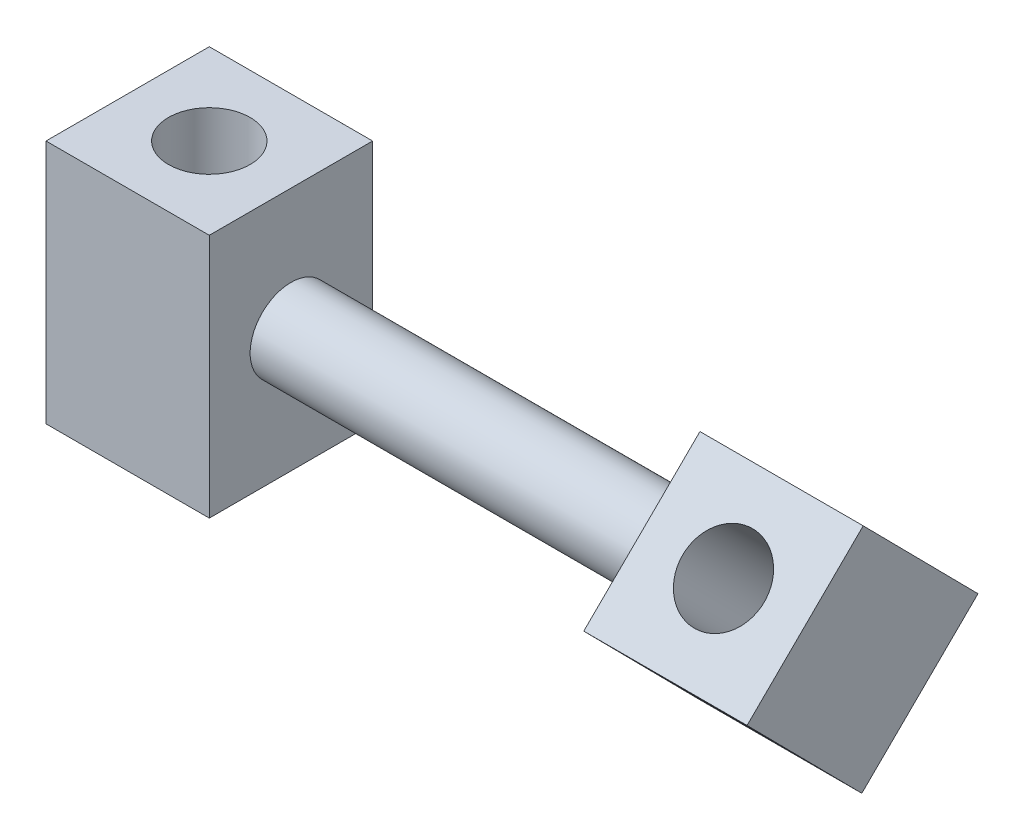
SolidWorks part; units mm, degrees
ref_plane "前视基准面" through (0, 0, 0) normal (0, 0, 1) x (1, 0, 0)
ref_plane "上视基准面" through (0, 0, 0) normal (0, 1, 0) x (1, 0, 0)
ref_plane "右视基准面" through (0, 0, 0) normal (1, 0, 0) x (0, 0, -1)
sketch "草图1" plane through (0, 0, 0) normal (0, 1, 0) x (1, 0, 0)
  line L1 (-10, -10) -> (10, -10)
  line L2 (-10, -10) -> (-10, 10)
  line L3 (-10, 10) -> (10, 10)
  line L4 (10, -10) -> (10, 10)
  line L5 (-10, -10) -> (10, 10) construction
  line L6 (-10, 10) -> (10, -10) construction
  point P0 (0, 0)
  dimension "D1" = 20
  dimension "D2" = 20
extrude "凸台-拉伸1" add sketch "草图1" along normal blind 30
sketch "草图2" plane through (10, 0, 0) normal (1, 0, 0) x (0, 0, -1)
  line L0 (-10, 15) -> (10, 15) construction
  line L1 (-10, 30) -> (-10, 0) construction
  line L2 (10, 30) -> (10, 0) construction
  circle A0 centre (0, 15) radius 5
  dimension "D1" = 10
extrude "凸台-拉伸2" add sketch "草图2" along normal blind 50
sketch "草图3" plane through (60, 0, 0) normal (1, 0, 0) x (0, 0, -1)
  line L0 (-10, 15) -> (10, 15) construction
  line L1 (-10, 30) -> (-10, 0) construction
  line L2 (10, 30) -> (10, 0) construction
  line L3 (0, 30) -> (0, 0) construction
  line L4 (-10, 30) -> (10, 30) construction
  line L5 (0, 15) -> (6.2443, 21.2443) construction
  line L6 (-14.1419, 15.0855) -> (0.0855, 29.1419)
  line L7 (-14.1419, 15.0855) -> (-0.0855, 0.8581)
  line L8 (0.0855, 29.1419) -> (14.1419, 14.9145)
  line L9 (-0.0855, 0.8581) -> (14.1419, 14.9145)
  line L10 (-14.1419, 15.0855) -> (14.1419, 14.9145) construction
  line L11 (0.0855, 29.1419) -> (-0.0855, 0.8581) construction
  dimension "D1" = 45
  dimension "D2" = 20
  dimension "D3" = 20
extrude "凸台-拉伸3" add sketch "草图3" along normal blind 20
sketch "草图4" plane through (0, 30, 0) normal (0, 1, 0) x (1, 0, 0)
  circle A0 centre (0, 0) radius 5
  dimension "D1" = 10
extrude "切除-拉伸1" cut sketch "草图4" against normal up to next
sketch "草图5" plane through (0, 14.7044, 14.5276) normal (0, 0.7114, 0.7028) x (1, 0, 0)
  line L0 (60, 10.5423) -> (80, 10.5423) construction
  line L1 (60, 20.5423) -> (60, 0.5423) construction
  line L2 (80, 20.5423) -> (80, 0.5423) construction
  circle A0 centre (70, 10.5423) radius 5
  dimension "D1" = 10
extrude "切除-拉伸2" cut sketch "草图5" against normal up to next
ref_axis "基准轴1" through (0, 0, 0) along (0, 1, 0)
ref_axis "基准轴2" through (70, 4.3297, -10.542) along (0, 0.7114, 0.7028)
